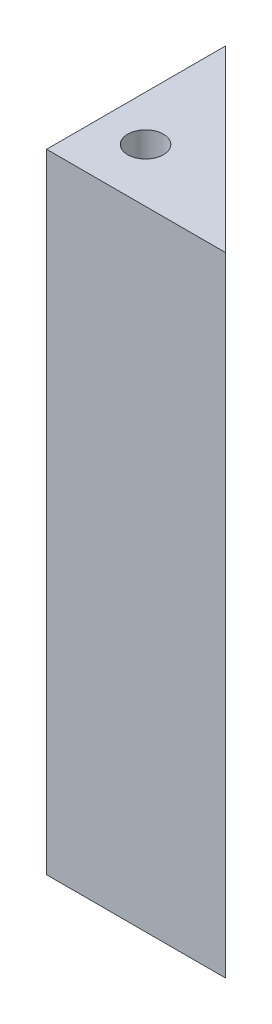
SolidWorks part; units mm, degrees
ref_plane "Front Plane" through (0, 0, 0) normal (0, 0, 1) x (1, 0, 0)
ref_plane "Top Plane" through (0, 0, 0) normal (0, 1, 0) x (1, 0, 0)
ref_plane "Right Plane" through (0, 0, 0) normal (1, 0, 0) x (0, 0, -1)
sketch "Sketch1" plane through (0, 0, 0) normal (0, 1, 0) x (1, 0, 0)
  line L0 (0, 0) -> (0, -15)
  line L1 (0, -15) -> (15, -15)
  line L2 (15, -15) -> (0, 0)
  circle A0 centre (3.8, -10.5) radius 1.5
  dimension "D3" = 3.8
  dimension "D5" = 3
  dimension "D1" = 15
  dimension "D2" = 15
  dimension "D4" = 4.5
extrude "Boss-Extrude1" add sketch "Sketch1" along normal blind 5
extrude "Boss-Extrude2" add sketch "Sketch1<2>" along direction (0, -1, 0) on the side against the normal blind 42.7 contours A0 | L1 L2 L0 A0 region at (7.35, 0, 7.65) region at (3.8, 0, 10.5)
sketch "Sketch1<2>" plane through (0, 0, 0) normal (0, 1, 0) x (1, 0, 0) same geometry as "Sketch1"
extrude "Boss-Extrude3" add sketch "Sketch1<4>" against normal blind 5 from offset 42.7 contours L1 L2 L0 A0 region at (7.35, 0, 7.65) offset against normal yes
sketch "Sketch1<4>" plane through (0, 0, 0) normal (0, 1, 0) x (1, 0, 0) same geometry as "Sketch1"
